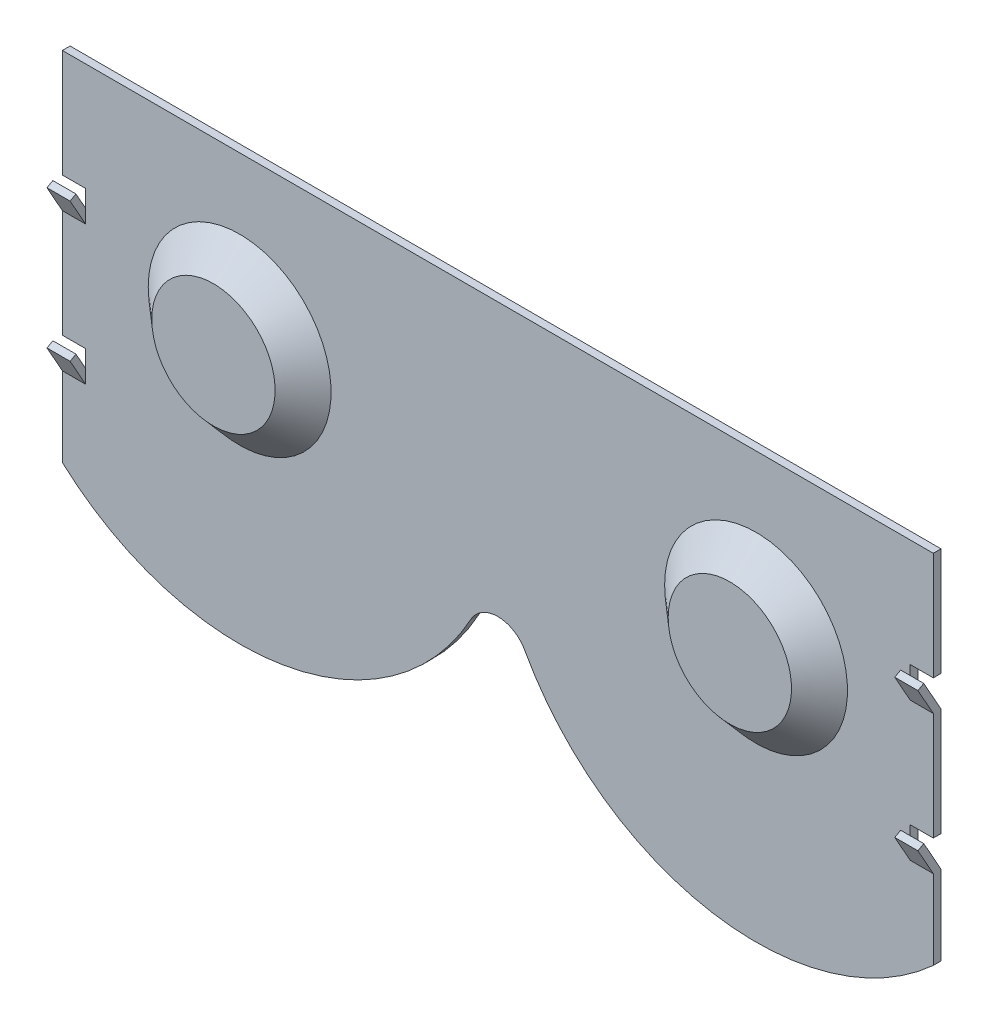
SolidWorks part; units mm, degrees
ref_plane "Plan de face" through (0, 0, 0) normal (0, 0, 1) x (1, 0, 0)
ref_plane "Plan de dessus" through (0, 0, 0) normal (0, 1, 0) x (1, 0, 0)
ref_plane "Plan de droite" through (0, 0, 0) normal (1, 0, 0) x (0, 0, -1)
sketch "Esquisse1" plane through (0, 0, 0) normal (0, 0, 1) x (1, 0, 0)
  line L0 (-28.25, 0) -> (28.25, 0)
  line L1 (28.25, 0) -> (28.25, -23.1554) construction
  line L2 (0, 0) -> (0, -40.6315) construction
  line L3 (-25.9242, -10.5) -> (28.25, -10.5) construction
  line L4 (-28.25, -7) -> (28.25, -7) construction
  line L5 (-28.25, -16) -> (28.25, -16) construction
  line L6 (-28.25, 0) -> (-28.25, -23.1554) construction
  line L7 (28.25, 0) -> (28.25, -7)
  line L8 (28.25, -7) -> (26.75, -7)
  line L10 (28.25, -9) -> (26.75, -9)
  line L11 (26.75, -7) -> (26.75, -9)
  line L12 (28.25, -16) -> (26.75, -16)
  line L14 (28.25, -18) -> (26.75, -18)
  line L15 (26.75, -16) -> (26.75, -18)
  line L16 (28.25, -9) -> (28.25, -16)
  line L17 (28.25, -18) -> (28.25, -23.1554)
  line L18 (-28.25, -18) -> (-28.25, -23.1554)
  line L19 (-28.25, -18) -> (-26.75, -18)
  line L20 (-26.75, -16) -> (-26.75, -18)
  line L21 (-28.25, -16) -> (-26.75, -16)
  line L22 (-28.25, -9) -> (-28.25, -16)
  line L23 (-28.25, -9) -> (-26.75, -9)
  line L24 (-26.75, -7) -> (-26.75, -9)
  line L25 (-28.25, -7) -> (-26.75, -7)
  line L26 (-28.25, 0) -> (-28.25, -7)
  line L27 (-23.4635, -27.6) -> (-11.2217, -27.6) construction
  arc A0 (28.25, -23.1554) -> (1.7539, -18.7175) centre (16.75, -10.5) cw
  arc A1 (1.7539, -18.7175) -> (-1.7539, -18.7175) centre (0, -19.6786) ccw
  arc A2 (-1.7539, -18.7175) -> (-28.25, -23.1554) centre (-16.75, -10.5) cw
  dimension "D3" = 10.5
  dimension "D6" = 2
  dimension "D10" = 2
  dimension "D11" = 33.5
  dimension "D12" = 27.6
  dimension "D1" = 56.5
  dimension "D2" = 56.5
  dimension "D4" = 7
  dimension "D5" = 16
  dimension "D7" = 2
  dimension "D8" = 1.5
extrude "Boss.-Extru.1" add sketch "Esquisse1" along normal blind 0.5
ref_plane "Plan1" through (0, -10.5, 0) normal (0, -1, 0) x (1, 0, 0)
sketch "Esquisse2" plane through (0, -10.5, 0) normal (0, -1, 0) x (1, 0, 0)
  line L0 (-16.75, 0) -> (-16.75, 2.2)
  line L2 (-16.75, 2.2) -> (-12.75, 2.2)
  line L3 (-12.75, 2.2) -> (-10.25, 0)
  line L4 (-16.75, 0) -> (-10.25, 0)
  line L7 (0, 0) -> (0, 10.798) construction
  line L8 (-28.25, 0) -> (-1.7539, 0) construction
  dimension "D1" = 4
  dimension "D2" = 6.5
  dimension "D3" = 2.2
  dimension "D4" = 16.75
revolve "Révolution1" add sketch "Esquisse2" angle 360 about L0
sketch "Esquisse3" plane through (0, -10.5, 0) normal (0, -1, 0) x (1, 0, 0)
  line L0 (1.7539, 0) -> (28.25, 0) construction
  line L2 (16.75, 0) -> (16.75, 2.2)
  line L3 (16.75, 2.2) -> (20.75, 2.2)
  line L4 (20.75, 2.2) -> (23.25, 0)
  line L5 (16.75, 0) -> (23.25, 0)
  dimension "D1" = 4
  dimension "D2" = 6.5
  dimension "D3" = 2.2
  dimension "D4" = 16.75
revolve "Révolution2" add sketch "Esquisse3" angle 360 about L2
sketch "Esquisse5" plane through (28.25, 0, 0) normal (1, 0, 0) x (0, 0, -1)
  line L0 (0, -18) -> (-1.1192, -16)
  line L1 (-1.1192, -16) -> (-1.5, -16.2131)
  line L2 (-1.5, -16.2131) -> (-0.5, -18)
  line L3 (-0.5, -18) -> (0, -18) construction
  line L4 (-0.5, -23.1554) -> (-0.5, -18) construction
  line L5 (-0.5, -18) -> (0, -18)
  line L6 (-0.5, -16) -> (0, -16) construction
  line L7 (0, -18) -> (0, -16) construction
  line L8 (-0.5, -9) -> (-1.5, -7.2131)
  line L9 (-1.5, -7.2131) -> (-1.1192, -7)
  line L10 (-1.1192, -7) -> (0, -9)
  line L11 (0, -9) -> (-0.5, -9)
  line L12 (-0.5, -7) -> (0, -7) construction
  dimension "D1" = 1.5
extrude "Boss.-Extru.2" add sketch "Esquisse5" against normal blind 1.5
extrude "Boss.-Extru.3" add sketch "Esquisse5<2>" against normal blind 1.5 from surface starting at face at (-26.75, -17, 0.25)
sketch "Esquisse5<2>" plane through (28.25, 0, 0) normal (1, 0, 0) x (0, 0, -1) same geometry as "Esquisse5"
